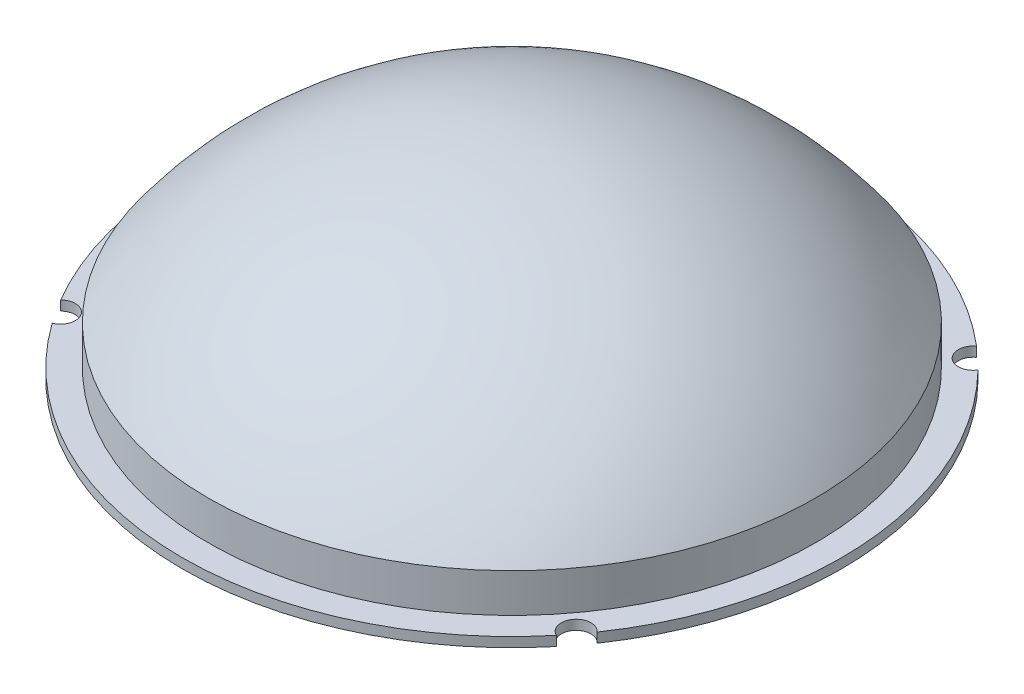
SolidWorks part; units mm, degrees
material "ABS"
ref_plane "Front Plane" through (0, 0, 0) normal (0, 0, 1) x (1, 0, 0)
ref_plane "Top Plane" through (0, 0, 0) normal (0, 1, 0) x (1, 0, 0)
ref_plane "Right Plane" through (0, 0, 0) normal (1, 0, 0) x (0, 0, -1)
sketch "Sketch1" plane through (0, 0, 0) normal (0, 1, 0) x (1, 0, 0)
  circle A0 centre (0, 0) radius 59.69
  dimension "D1" = 119.38
extrude "Dome Base" add sketch "Sketch1" along normal blind 9.525
dome "Dome1" faces to dome 1 distance 30.48 reverse direction no elliptical dome no face at (0, 9.525, 59.69) parameters "D1"=30.48
shell "Shell1" thickness 1.905 removed face at (0, 0, 59.69)
sketch "Sketch2" plane through (0, 0, 0) normal (0, -1, 0) x (1, 0, 0)
  circle A0 centre (0, 0) radius 64.77
  circle A1 centre (0, 0) radius 59.69
  circle A2 centre (0, 0) radius 59.69
  dimension "D1" = 0
  dimension "D2" = 5.08
extrude "Boss-Extrude2" add sketch "Sketch2" against normal blind 1.905
sketch "Sketch3" plane through (0, 1.905, 0) normal (0, 1, 0) x (1, 0, 0)
  line L0 (0, 0) -> (-61.5718, -39.9852) construction
  line L1 (0, 0) -> (58.232, -43.881) construction
  line L2 (0, 0) -> (-46.7778, 55.7476) construction
  line L3 (0, 0) -> (43.74, 46.9054) construction
  line L4 (43.74, 46.9054) -> (50.4825, 54.1359) construction
  line L5 (0, -22.0027) -> (0, 22.0027) construction
  circle A0 centre (0, 0) radius 64.135 construction
  circle A1 centre (-53.7881, -34.9304) radius 2.921
  circle A2 centre (51.2205, -38.5974) radius 2.921
  circle A3 centre (-41.2252, 49.1303) radius 2.921
  circle A4 centre (43.74, 46.9054) radius 2.921
  dimension "D1" = 128.27
  dimension "D2" = 5.842
  dimension "D3" = 5.842
  dimension "D4" = 5.842
  dimension "D5" = 5.842
  dimension "D6" = 40
  dimension "D7" = 43
  dimension "D8" = 53
  dimension "D9" = 57
extrude "Cut-Extrude1" cut sketch "Sketch3" against normal through all
